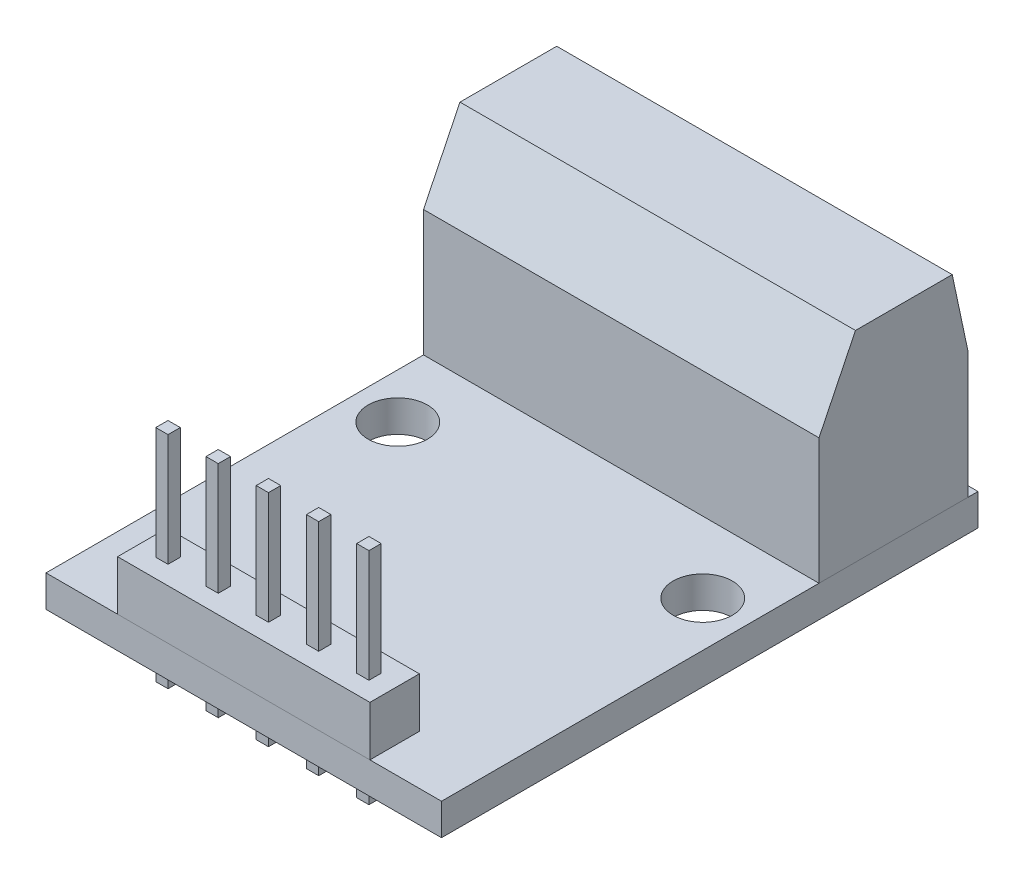
SolidWorks part; units mm, degrees
ref_plane "Front Plane" through (0, 0, 0) normal (0, 0, 1) x (1, 0, 0)
ref_plane "Top Plane" through (0, 0, 0) normal (0, 1, 0) x (1, 0, 0)
ref_plane "Right Plane" through (0, 0, 0) normal (1, 0, 0) x (0, 0, -1)
sketch "Sketch1" plane through (0, 0, 0) normal (0, 1, 0) x (1, 0, 0)
  line L1 (10, -13.565) -> (-10, -13.565)
  line L2 (10, -13.565) -> (10, 13.565)
  line L3 (10, 13.565) -> (-10, 13.565)
  line L4 (-10, -13.565) -> (-10, 13.565)
  line L5 (10, -13.565) -> (-10, 13.565) construction
  line L6 (10, 13.565) -> (-10, -13.565) construction
  point P0 (0, 0)
  dimension "D1" = 27.13
  dimension "D2" = 20
extrude "Boss-Extrude1" add sketch "Sketch1" along normal blind 1.6
sketch "Sketch2" plane through (0, 1.6, 0) normal (0, 1, 0) x (1, 0, 0)
  line L0 (-10, -13.565) -> (10, -13.565) construction
  line L1 (-6.38, -13.565) -> (6.38, -13.565)
  line L2 (-6.38, -13.565) -> (-6.38, -11.065)
  line L3 (-6.38, -11.065) -> (6.38, -11.065)
  line L4 (6.38, -13.565) -> (6.38, -11.065)
  point P6 (0, -11.065)
  dimension "D1" = 2.5
  dimension "D2" = 12.76
extrude "Boss-Extrude2" add sketch "Sketch2" along normal blind 2.52 separate body
sketch "Sketch3" plane through (0, 4.12, 0) normal (0, 1, 0) x (1, 0, 0)
  line L0 (-6.38, -11.065) -> (-6.38, -13.565) construction
  line L1 (-5.39, -12.005) -> (-4.77, -12.005)
  line L2 (-5.39, -12.005) -> (-5.39, -12.625)
  line L3 (-5.39, -12.625) -> (-4.77, -12.625)
  line L4 (-4.77, -12.005) -> (-4.77, -12.625)
  line L5 (-5.39, -12.005) -> (-4.77, -12.625) construction
  line L6 (-5.39, -12.625) -> (-4.77, -12.005) construction
  line L7 (-2.85, -12.005) -> (-2.23, -12.005)
  line L8 (-2.85, -12.005) -> (-2.85, -12.625)
  line L9 (-2.85, -12.625) -> (-2.23, -12.625)
  line L10 (-2.23, -12.005) -> (-2.23, -12.625)
  line L11 (-2.85, -12.005) -> (-2.23, -12.625) construction
  line L12 (-2.85, -12.625) -> (-2.23, -12.005) construction
  line L13 (-0.31, -12.005) -> (0.31, -12.005)
  line L14 (-0.31, -12.005) -> (-0.31, -12.625)
  line L15 (-0.31, -12.625) -> (0.31, -12.625)
  line L16 (0.31, -12.005) -> (0.31, -12.625)
  line L17 (-0.31, -12.005) -> (0.31, -12.625) construction
  line L18 (-0.31, -12.625) -> (0.31, -12.005) construction
  line L19 (2.23, -12.005) -> (2.85, -12.005)
  line L20 (2.23, -12.005) -> (2.23, -12.625)
  line L21 (2.23, -12.625) -> (2.85, -12.625)
  line L22 (2.85, -12.005) -> (2.85, -12.625)
  line L23 (2.23, -12.005) -> (2.85, -12.625) construction
  line L24 (2.23, -12.625) -> (2.85, -12.005) construction
  line L25 (4.77, -12.005) -> (5.39, -12.005)
  line L26 (4.77, -12.005) -> (4.77, -12.625)
  line L27 (4.77, -12.625) -> (5.39, -12.625)
  line L28 (5.39, -12.005) -> (5.39, -12.625)
  line L29 (4.77, -12.005) -> (5.39, -12.625) construction
  line L30 (4.77, -12.625) -> (5.39, -12.005) construction
  point P0 (-5.08, -12.315)
  point P7 (-6.38, -12.315)
  point P10 (-2.54, -12.315)
  point P15 (0, -12.315)
  point P20 (2.54, -12.315)
  point P25 (5.08, -12.315)
  dimension "D1" = 5
  dimension "D2" = 0.62
  dimension "D3" = 10.78
extrude "Boss-Extrude3" add sketch "Sketch3" along normal blind 5.68 and the other way blind 5.45 separate body
sketch "Sketch4" plane through (0, 1.6, 0) normal (0, 1, 0) x (1, 0, 0)
  line L0 (-10, 13.565) -> (-10, -13.565) construction
  line L1 (10, 5.525) -> (-10, 5.525)
  line L2 (10, 5.525) -> (10, 13.065)
  line L3 (10, 13.065) -> (-10, 13.065)
  line L4 (-10, 5.525) -> (-10, 13.065)
  line L5 (10, 5.525) -> (-10, 13.065) construction
  line L6 (10, 13.065) -> (-10, 5.525) construction
  line L7 (10, -13.565) -> (10, 13.565) construction
  line L8 (10, 13.565) -> (-10, 13.565) construction
  point P0 (0, 9.295)
  dimension "D1" = 7.54
  dimension "D2" = 0.5
extrude "Boss-Extrude4" add sketch "Sketch4" along normal blind 10.15 separate body
sketch "Sketch5" plane through (0, 0, -13.065) normal (0, 0, -1) x (-1, 0, 0)
  line L0 (-10, 0) -> (10, 0) construction
  line L1 (-9.28, 7.97) -> (-5.18, 7.97)
  line L2 (-9.28, 7.97) -> (-9.28, 2.37)
  line L3 (-9.28, 2.37) -> (-5.18, 2.37)
  line L4 (-5.18, 7.97) -> (-5.18, 2.37)
  line L5 (-4.46, 7.97) -> (-0.36, 7.97)
  line L6 (-0.36, 7.97) -> (-0.36, 2.37)
  line L7 (-4.46, 2.37) -> (-0.36, 2.37)
  line L8 (-4.46, 7.97) -> (-4.46, 2.37)
  line L9 (0.36, 7.97) -> (4.46, 7.97)
  line L10 (4.46, 7.97) -> (4.46, 2.37)
  line L11 (0.36, 2.37) -> (4.46, 2.37)
  line L12 (0.36, 7.97) -> (0.36, 2.37)
  line L13 (5.18, 7.97) -> (9.28, 7.97)
  line L14 (9.28, 7.97) -> (9.28, 2.37)
  line L15 (5.18, 2.37) -> (9.28, 2.37)
  line L16 (5.18, 7.97) -> (5.18, 2.37)
  line L17 (-9.28, 7.97) -> (-10, 7.97) construction
  line L18 (-10, 11.75) -> (-10, 1.6) construction
  line L19 (9.28, 7.97) -> (10, 7.97) construction
  line L20 (10, 11.75) -> (10, 1.6) construction
  line L21 (-5.18, 7.97) -> (-4.46, 7.97) construction
  dimension "D1" = 4.1
  dimension "D2" = 5.6
  dimension "D3" = 2.37
  dimension "D4" = 4
extrude "Cut-Extrude1" cut sketch "Sketch5" against normal blind 4
chamfer "Chamfer1" distance 3.78 angle 12 1 edges at (0, 11.75, -13.065) first distance on face at (7.23, 5.17, -13.065)
chamfer "Chamfer2" distance 3.78 angle 26 1 edges at (0, 11.75, -5.525) first distance on face at (0, 6.675, -5.525)
sketch "Sketch6" plane through (0, 1.6, 0) normal (0, 1, 0) x (1, 0, 0)
  line L0 (-7.71, 1.935) -> (7.71, 1.935) construction
  line L1 (-10, -13.565) -> (10, -13.565) construction
  circle A0 centre (-7.71, 1.935) radius 1.5
  circle A1 centre (7.71, 1.935) radius 1.5
  point P4 (0, 1.935)
  dimension "D1" = 3
  dimension "D2" = 15.42
  dimension "D3" = 15.5
extrude "Cut-Extrude2" cut sketch "Sketch6" against normal through all
